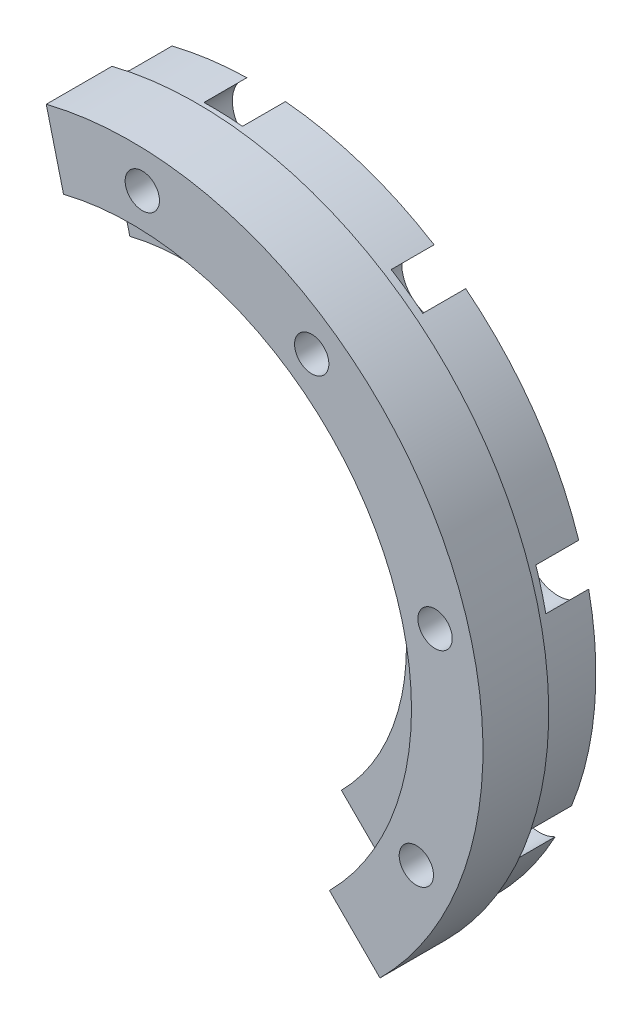
SolidWorks part; units mm, degrees
ref_plane "Front Plane" through (0, 0, 0) normal (0, 0, 1) x (1, 0, 0)
ref_plane "Top Plane" through (0, 0, 0) normal (0, 1, 0) x (1, 0, 0)
ref_plane "Right Plane" through (0, 0, 0) normal (1, 0, 0) x (0, 0, -1)
ref_plane "PZ_p24_600" through (0, 0, 24.6) normal (0, 0, 1) x (1, 0, 0)
sketch "S_prism1" plane through (0, 0, 24.6) normal (0, 0, 1) x (1, 0, 0)
  line L0 (-5.9513, 23.8693) -> (-4.7417, 19.0178)
  line L1 (13.8593, -13.8593) -> (17.3948, -17.3948)
  arc A0 (17.3948, -17.3948) -> (-5.9513, 23.8693) centre (0, 0) ccw
  arc A1 (-4.7417, 19.0178) -> (13.8593, -13.8593) centre (0, 0) cw
extrude "Boss_1" add sketch "S_prism1" along normal blind 5.6
ref_plane "PZ_p21_600" through (0, 0, 21.6) normal (0, 0, 1) x (1, 0, 0)
sketch "S_prism2" plane through (0, 0, 21.6) normal (0, 0, 1) x (1, 0, 0)
  line L0 (-5.7536, 23.1971) -> (-3.7555, 15.1412)
  line L1 (11.0443, -11.0174) -> (16.9205, -16.8792)
  arc A0 (16.9205, -16.8792) -> (-5.7536, 23.1971) centre (0, 0) ccw
  arc A1 (-3.7555, 15.1412) -> (11.0443, -11.0174) centre (0, 0) cw
extrude "Boss_2" add sketch "S_prism2" along normal blind 4.95
ref_plane "PZ_p24_500" through (0, 0, 24.5) normal (0, 0, 1) x (1, 0, 0)
sketch "S_pcut3" plane through (0, 0, 24.5) normal (0, 0, 1) x (1, 0, 0)
  line L0 (-6.4187, 23.955) -> (-6.1858, 23.0856)
  line L1 (16.6023, -17.1922) -> (17.2275, -17.8396)
  arc A0 (17.2275, -17.8396) -> (-6.4187, 23.955) centre (0, 0) ccw
  arc A1 (-6.1858, 23.0856) -> (16.6023, -17.1922) centre (0, 0) cw
extrude "Cut_3" cut sketch "S_pcut3" along normal blind 1.1
ref_plane "PZ_p21_500" through (0, 0, 21.5) normal (0, 0, 1) x (1, 0, 0)
sketch "S_pcut4" plane through (0, 0, 21.5) normal (0, 0, 1) x (1, 0, 0)
  line L0 (-4.3999, 16.4207) -> (-4.0117, 14.9719)
  line L1 (10.7672, -11.1498) -> (11.8092, -12.2288)
  arc A0 (11.8092, -12.2288) -> (-4.3999, 16.4207) centre (0, 0) ccw
  arc A1 (-4.0117, 14.9719) -> (10.7672, -11.1498) centre (0, 0) cw
extrude "Cut_4" cut sketch "S_pcut4" along normal blind 1.1
sketch "S_hole5" plane through (0, 0, 21.5) normal (0, 0, 1) x (1, 0, 0)
  circle A0 centre (19.9388, -9.2976) radius 1.2
  dimension "D1_S_hole5" = 2.4
  dimension "P2" = 19.9388
  dimension "P3" = 9.2976
extrude "Hole_5" cut sketch "S_hole5" along normal blind 8.8
sketch "S_hole6" plane through (0, 0, 21.5) normal (0, 0, 1) x (1, 0, 0)
  circle A0 centre (19.9388, -9.2976) radius 2.3
  dimension "D1_S_hole6" = 4.6
  dimension "P2" = 19.9388
  dimension "P3" = 9.2976
extrude "Hole_6" cut sketch "S_hole6" along normal blind 3.1
sketch "S_hole7" plane through (0, 0, 21.5) normal (0, 0, 1) x (1, 0, 0)
  circle A0 centre (21.2504, 5.694) radius 1.2
  dimension "D1_S_hole7" = 2.4
  dimension "P2" = 21.2504
  dimension "P3" = 5.694
extrude "Hole_7" cut sketch "S_hole7" along normal blind 8.8
sketch "S_hole8" plane through (0, 0, 21.5) normal (0, 0, 1) x (1, 0, 0)
  circle A0 centre (21.2504, 5.694) radius 2.3
  dimension "D1_S_hole8" = 4.6
  dimension "P2" = 21.2504
  dimension "P3" = 5.694
extrude "Hole_8" cut sketch "S_hole8" along normal blind 3.1
sketch "S_hole9" plane through (0, 0, 21.5) normal (0, 0, 1) x (1, 0, 0)
  circle A0 centre (12.6187, 18.0213) radius 1.2
  dimension "D1_S_hole9" = 2.4
  dimension "P2" = 12.6187
  dimension "P3" = 18.0213
extrude "Hole_9" cut sketch "S_hole9" along normal blind 8.8
sketch "S_hole10" plane through (0, 0, 21.5) normal (0, 0, 1) x (1, 0, 0)
  circle A0 centre (12.6187, 18.0213) radius 2.3
  dimension "D1_S_hole10" = 4.6
  dimension "P2" = 12.6187
  dimension "P3" = 18.0213
extrude "Hole_10" cut sketch "S_hole10" along normal blind 3.1
sketch "S_hole11" plane through (0, 0, 21.5) normal (0, 0, 1) x (1, 0, 0)
  circle A0 centre (0.7678, 21.9866) radius 1.2
  dimension "D1_S_hole11" = 2.4
  dimension "P2" = 0.7678
  dimension "P3" = 21.9866
extrude "Hole_11" cut sketch "S_hole11" along normal blind 8.8
sketch "S_hole12" plane through (0, 0, 21.5) normal (0, 0, 1) x (1, 0, 0)
  circle A0 centre (0.7678, 21.9866) radius 2.3
  dimension "D1_S_hole12" = 4.6
  dimension "P2" = 0.7678
  dimension "P3" = 21.9866
extrude "Hole_12" cut sketch "S_hole12" along normal blind 3.1
equation "\"plate_t\" = 3"
equation "\"clearance\" = 0.5"
